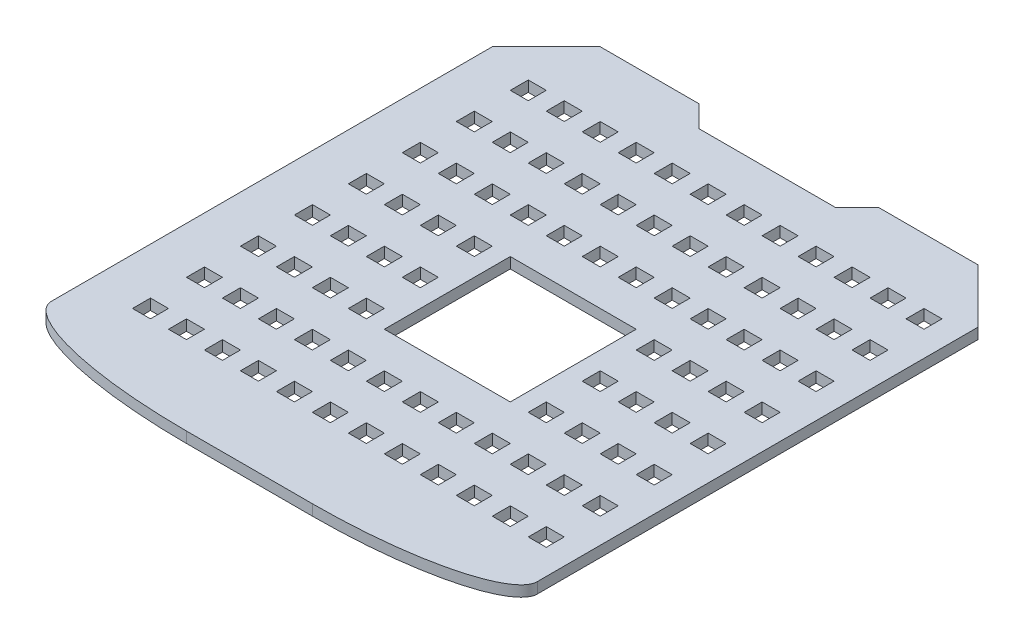
SolidWorks part; units mm, degrees
material "Balsa"
ref_plane "Front Plane" through (0, 0, 0) normal (0, 0, 1) x (1, 0, 0)
ref_plane "Top Plane" through (0, 0, 0) normal (0, 1, 0) x (1, 0, 0)
ref_plane "Right Plane" through (0, 0, 0) normal (1, 0, 0) x (0, 0, -1)
sketch "Sketch1" plane through (0, 0, 0) normal (0, 1, 0) x (1, 0, 0)
  line L1 (-67.5, 75) -> (67.5, 75)
  line L2 (-67.5, 75) -> (-67.5, -75)
  line L3 (-67.5, -75) -> (67.5, -75)
  line L4 (67.5, 75) -> (67.5, -75)
  line L5 (-67.5, 75) -> (67.5, -75) construction
  line L6 (-67.5, -75) -> (67.5, 75) construction
  point P0 (0, 0)
  dimension "D1" = 135
  dimension "D2" = 150
extrude "Boss-Extrude1" add sketch "Sketch1" along normal blind 3
sketch "Sketch2" plane through (0, 3, 0) normal (0, 1, 0) x (1, 0, 0)
  line L5 (-67.5, 75) -> (-67.5, -75) construction
  line L6 (-44.5, -53) -> (-44.5, -48)
  line L1140 (-54.5, -53) -> (-54.5, -48)
  line L1141 (-54.5, -53) -> (-49.5, -53)
  line L1142 (-49.5, -53) -> (-49.5, -48)
  line L1143 (-54.5, -48) -> (-49.5, -48)
  line L1144 (-44.5, -48) -> (-39.5, -48)
  line L1145 (-67.5, -75) -> (67.5, -75) construction
  line L1146 (-39.5, -53) -> (-39.5, -48)
  line L1249 (-44.5, -53) -> (-39.5, -53)
  line L1250 (-34.5, -53) -> (-34.5, -48)
  line L1251 (-34.5, -48) -> (-29.5, -48)
  line L1252 (-29.5, -53) -> (-29.5, -48)
  line L1253 (-34.5, -53) -> (-29.5, -53)
  line L1254 (-24.5, -53) -> (-24.5, -48)
  line L1255 (-24.5, -48) -> (-19.5, -48)
  line L1256 (-19.5, -53) -> (-19.5, -48)
  line L1257 (-24.5, -53) -> (-19.5, -53)
  line L1258 (-14.5, -53) -> (-14.5, -48)
  line L1259 (-14.5, -48) -> (-9.5, -48)
  line L1260 (-9.5, -53) -> (-9.5, -48)
  line L1261 (-14.5, -53) -> (-9.5, -53)
  line L1262 (-4.5, -53) -> (-4.5, -48)
  line L1263 (-4.5, -48) -> (0.5, -48)
  line L1264 (0.5, -53) -> (0.5, -48)
  line L1265 (-4.5, -53) -> (0.5, -53)
  line L1266 (5.5, -53) -> (5.5, -48)
  line L1267 (5.5, -48) -> (10.5, -48)
  line L1268 (10.5, -53) -> (10.5, -48)
  line L1269 (5.5, -53) -> (10.5, -53)
  line L1270 (15.5, -53) -> (15.5, -48)
  line L1271 (15.5, -48) -> (20.5, -48)
  line L1272 (20.5, -53) -> (20.5, -48)
  line L1273 (15.5, -53) -> (20.5, -53)
  line L1274 (25.5, -53) -> (25.5, -48)
  line L1275 (25.5, -48) -> (30.5, -48)
  line L1276 (30.5, -53) -> (30.5, -48)
  line L1277 (25.5, -53) -> (30.5, -53)
  line L1278 (35.5, -53) -> (35.5, -48)
  line L1279 (35.5, -48) -> (40.5, -48)
  line L1280 (40.5, -53) -> (40.5, -48)
  line L1281 (35.5, -53) -> (40.5, -53)
  line L1282 (45.5, -53) -> (45.5, -48)
  line L1283 (45.5, -48) -> (50.5, -48)
  line L1284 (50.5, -53) -> (50.5, -48)
  line L1285 (45.5, -53) -> (50.5, -53)
  line L1286 (55.5, -53) -> (55.5, -48)
  line L1287 (55.5, -48) -> (60.5, -48)
  line L1288 (60.5, -53) -> (60.5, -48)
  line L1289 (55.5, -53) -> (60.5, -53)
  line L1290 (-44.5, -38) -> (-44.5, -33)
  line L1291 (-44.5, -33) -> (-39.5, -33)
  line L1292 (-39.5, -38) -> (-39.5, -33)
  line L1293 (-44.5, -38) -> (-39.5, -38)
  line L1294 (-34.5, -38) -> (-34.5, -33)
  line L1295 (-34.5, -33) -> (-29.5, -33)
  line L1296 (-29.5, -38) -> (-29.5, -33)
  line L1297 (-34.5, -38) -> (-29.5, -38)
  line L1298 (-24.5, -38) -> (-24.5, -33)
  line L1299 (-24.5, -33) -> (-19.5, -33)
  line L1300 (-19.5, -38) -> (-19.5, -33)
  line L1301 (-24.5, -38) -> (-19.5, -38)
  line L1302 (-14.5, -38) -> (-14.5, -33)
  line L1303 (-14.5, -33) -> (-9.5, -33)
  line L1304 (-9.5, -38) -> (-9.5, -33)
  line L1305 (-14.5, -38) -> (-9.5, -38)
  line L1306 (-4.5, -38) -> (-4.5, -33)
  line L1307 (-4.5, -33) -> (0.5, -33)
  line L1308 (0.5, -38) -> (0.5, -33)
  line L1309 (-4.5, -38) -> (0.5, -38)
  line L1310 (5.5, -38) -> (5.5, -33)
  line L1311 (5.5, -33) -> (10.5, -33)
  line L1312 (10.5, -38) -> (10.5, -33)
  line L1313 (5.5, -38) -> (10.5, -38)
  line L1314 (15.5, -38) -> (15.5, -33)
  line L1315 (15.5, -33) -> (20.5, -33)
  line L1316 (20.5, -38) -> (20.5, -33)
  line L1317 (15.5, -38) -> (20.5, -38)
  line L1318 (25.5, -38) -> (25.5, -33)
  line L1319 (25.5, -33) -> (30.5, -33)
  line L1320 (30.5, -38) -> (30.5, -33)
  line L1321 (25.5, -38) -> (30.5, -38)
  line L1322 (35.5, -38) -> (35.5, -33)
  line L1323 (35.5, -33) -> (40.5, -33)
  line L1324 (40.5, -38) -> (40.5, -33)
  line L1325 (35.5, -38) -> (40.5, -38)
  line L1326 (45.5, -38) -> (45.5, -33)
  line L1327 (45.5, -33) -> (50.5, -33)
  line L1328 (50.5, -38) -> (50.5, -33)
  line L1329 (45.5, -38) -> (50.5, -38)
  line L1330 (55.5, -38) -> (55.5, -33)
  line L1331 (55.5, -33) -> (60.5, -33)
  line L1332 (60.5, -38) -> (60.5, -33)
  line L1333 (55.5, -38) -> (60.5, -38)
  line L1334 (-44.5, -23) -> (-44.5, -18)
  line L1335 (-44.5, -18) -> (-39.5, -18)
  line L1336 (-39.5, -23) -> (-39.5, -18)
  line L1337 (-44.5, -23) -> (-39.5, -23)
  line L1338 (-34.5, -23) -> (-34.5, -18)
  line L1339 (-34.5, -18) -> (-29.5, -18)
  line L1340 (-29.5, -23) -> (-29.5, -18)
  line L1341 (-34.5, -23) -> (-29.5, -23)
  line L1342 (-24.5, -23) -> (-24.5, -18)
  line L1343 (-24.5, -18) -> (-19.5, -18)
  line L1344 (-19.5, -23) -> (-19.5, -18)
  line L1345 (-24.5, -23) -> (-19.5, -23)
  line L1346 (-14.5, -23) -> (-14.5, -18)
  line L1347 (-14.5, -18) -> (-9.5, -18)
  line L1348 (-9.5, -23) -> (-9.5, -18)
  line L1349 (-14.5, -23) -> (-9.5, -23)
  line L1350 (-4.5, -23) -> (-4.5, -18)
  line L1351 (-4.5, -18) -> (0.5, -18)
  line L1352 (0.5, -23) -> (0.5, -18)
  line L1353 (-4.5, -23) -> (0.5, -23)
  line L1354 (5.5, -23) -> (5.5, -18)
  line L1355 (5.5, -18) -> (10.5, -18)
  line L1356 (10.5, -23) -> (10.5, -18)
  line L1357 (5.5, -23) -> (10.5, -23)
  line L1358 (15.5, -23) -> (15.5, -18)
  line L1359 (15.5, -18) -> (20.5, -18)
  line L1360 (20.5, -23) -> (20.5, -18)
  line L1361 (15.5, -23) -> (20.5, -23)
  line L1362 (25.5, -23) -> (25.5, -18)
  line L1363 (25.5, -18) -> (30.5, -18)
  line L1364 (30.5, -23) -> (30.5, -18)
  line L1365 (25.5, -23) -> (30.5, -23)
  line L1366 (35.5, -23) -> (35.5, -18)
  line L1367 (35.5, -18) -> (40.5, -18)
  line L1368 (40.5, -23) -> (40.5, -18)
  line L1369 (35.5, -23) -> (40.5, -23)
  line L1370 (45.5, -23) -> (45.5, -18)
  line L1371 (45.5, -18) -> (50.5, -18)
  line L1372 (50.5, -23) -> (50.5, -18)
  line L1373 (45.5, -23) -> (50.5, -23)
  line L1374 (55.5, -23) -> (55.5, -18)
  line L1375 (55.5, -18) -> (60.5, -18)
  line L1376 (60.5, -23) -> (60.5, -18)
  line L1377 (55.5, -23) -> (60.5, -23)
  line L1378 (-44.5, -8) -> (-44.5, -3)
  line L1379 (-44.5, -3) -> (-39.5, -3)
  line L1380 (-39.5, -8) -> (-39.5, -3)
  line L1381 (-44.5, -8) -> (-39.5, -8)
  line L1382 (-34.5, -8) -> (-34.5, -3)
  line L1383 (-34.5, -3) -> (-29.5, -3)
  line L1384 (-29.5, -8) -> (-29.5, -3)
  line L1385 (-34.5, -8) -> (-29.5, -8)
  line L1386 (-24.5, -8) -> (-24.5, -3)
  line L1387 (-24.5, -3) -> (-19.5, -3)
  line L1388 (-19.5, -8) -> (-19.5, -3)
  line L1389 (-24.5, -8) -> (-19.5, -8)
  line L1390 (-14.5, -8) -> (-14.5, -3)
  line L1391 (-14.5, -3) -> (-9.5, -3)
  line L1392 (-9.5, -8) -> (-9.5, -3)
  line L1393 (-14.5, -8) -> (-9.5, -8)
  line L1394 (-4.5, -8) -> (-4.5, -3)
  line L1395 (-4.5, -3) -> (0.5, -3)
  line L1396 (0.5, -8) -> (0.5, -3)
  line L1397 (-4.5, -8) -> (0.5, -8)
  line L1398 (5.5, -8) -> (5.5, -3)
  line L1399 (5.5, -3) -> (10.5, -3)
  line L1400 (10.5, -8) -> (10.5, -3)
  line L1401 (5.5, -8) -> (10.5, -8)
  line L1402 (15.5, -8) -> (15.5, -3)
  line L1403 (15.5, -3) -> (20.5, -3)
  line L1404 (20.5, -8) -> (20.5, -3)
  line L1405 (15.5, -8) -> (20.5, -8)
  line L1406 (25.5, -8) -> (25.5, -3)
  line L1407 (25.5, -3) -> (30.5, -3)
  line L1408 (30.5, -8) -> (30.5, -3)
  line L1409 (25.5, -8) -> (30.5, -8)
  line L1410 (35.5, -8) -> (35.5, -3)
  line L1411 (35.5, -3) -> (40.5, -3)
  line L1412 (40.5, -8) -> (40.5, -3)
  line L1413 (35.5, -8) -> (40.5, -8)
  line L1414 (45.5, -8) -> (45.5, -3)
  line L1415 (45.5, -3) -> (50.5, -3)
  line L1416 (50.5, -8) -> (50.5, -3)
  line L1417 (45.5, -8) -> (50.5, -8)
  line L1418 (55.5, -8) -> (55.5, -3)
  line L1419 (55.5, -3) -> (60.5, -3)
  line L1420 (60.5, -8) -> (60.5, -3)
  line L1421 (55.5, -8) -> (60.5, -8)
  line L1422 (-44.5, 7) -> (-44.5, 12)
  line L1423 (-44.5, 12) -> (-39.5, 12)
  line L1424 (-39.5, 7) -> (-39.5, 12)
  line L1425 (-44.5, 7) -> (-39.5, 7)
  line L1426 (-34.5, 7) -> (-34.5, 12)
  line L1427 (-34.5, 12) -> (-29.5, 12)
  line L1428 (-29.5, 7) -> (-29.5, 12)
  line L1429 (-34.5, 7) -> (-29.5, 7)
  line L1430 (-24.5, 7) -> (-24.5, 12)
  line L1431 (-24.5, 12) -> (-19.5, 12)
  line L1432 (-19.5, 7) -> (-19.5, 12)
  line L1433 (-24.5, 7) -> (-19.5, 7)
  line L1434 (-14.5, 7) -> (-14.5, 12)
  line L1435 (-14.5, 12) -> (-9.5, 12)
  line L1436 (-9.5, 7) -> (-9.5, 12)
  line L1437 (-14.5, 7) -> (-9.5, 7)
  line L1438 (-4.5, 7) -> (-4.5, 12)
  line L1439 (-4.5, 12) -> (0.5, 12)
  line L1440 (0.5, 7) -> (0.5, 12)
  line L1441 (-4.5, 7) -> (0.5, 7)
  line L1442 (5.5, 7) -> (5.5, 12)
  line L1443 (5.5, 12) -> (10.5, 12)
  line L1444 (10.5, 7) -> (10.5, 12)
  line L1445 (5.5, 7) -> (10.5, 7)
  line L1446 (15.5, 7) -> (15.5, 12)
  line L1447 (15.5, 12) -> (20.5, 12)
  line L1448 (20.5, 7) -> (20.5, 12)
  line L1449 (15.5, 7) -> (20.5, 7)
  line L1450 (25.5, 7) -> (25.5, 12)
  line L1451 (25.5, 12) -> (30.5, 12)
  line L1452 (30.5, 7) -> (30.5, 12)
  line L1453 (25.5, 7) -> (30.5, 7)
  line L1454 (35.5, 7) -> (35.5, 12)
  line L1455 (35.5, 12) -> (40.5, 12)
  line L1456 (40.5, 7) -> (40.5, 12)
  line L1457 (35.5, 7) -> (40.5, 7)
  line L1458 (45.5, 7) -> (45.5, 12)
  line L1459 (45.5, 12) -> (50.5, 12)
  line L1460 (50.5, 7) -> (50.5, 12)
  line L1461 (45.5, 7) -> (50.5, 7)
  line L1462 (55.5, 7) -> (55.5, 12)
  line L1463 (55.5, 12) -> (60.5, 12)
  line L1464 (60.5, 7) -> (60.5, 12)
  line L1465 (55.5, 7) -> (60.5, 7)
  line L1466 (-44.5, 22) -> (-44.5, 27)
  line L1467 (-44.5, 27) -> (-39.5, 27)
  line L1468 (-39.5, 22) -> (-39.5, 27)
  line L1469 (-44.5, 22) -> (-39.5, 22)
  line L1470 (-34.5, 22) -> (-34.5, 27)
  line L1471 (-34.5, 27) -> (-29.5, 27)
  line L1472 (-29.5, 22) -> (-29.5, 27)
  line L1473 (-34.5, 22) -> (-29.5, 22)
  line L1474 (-24.5, 22) -> (-24.5, 27)
  line L1475 (-24.5, 27) -> (-19.5, 27)
  line L1476 (-19.5, 22) -> (-19.5, 27)
  line L1477 (-24.5, 22) -> (-19.5, 22)
  line L1478 (-14.5, 22) -> (-14.5, 27)
  line L1479 (-14.5, 27) -> (-9.5, 27)
  line L1480 (-9.5, 22) -> (-9.5, 27)
  line L1481 (-14.5, 22) -> (-9.5, 22)
  line L1482 (-4.5, 22) -> (-4.5, 27)
  line L1483 (-4.5, 27) -> (0.5, 27)
  line L1484 (0.5, 22) -> (0.5, 27)
  line L1485 (-4.5, 22) -> (0.5, 22)
  line L1486 (5.5, 22) -> (5.5, 27)
  line L1487 (5.5, 27) -> (10.5, 27)
  line L1488 (10.5, 22) -> (10.5, 27)
  line L1489 (5.5, 22) -> (10.5, 22)
  line L1490 (15.5, 22) -> (15.5, 27)
  line L1491 (15.5, 27) -> (20.5, 27)
  line L1492 (20.5, 22) -> (20.5, 27)
  line L1493 (15.5, 22) -> (20.5, 22)
  line L1494 (25.5, 22) -> (25.5, 27)
  line L1495 (25.5, 27) -> (30.5, 27)
  line L1496 (30.5, 22) -> (30.5, 27)
  line L1497 (25.5, 22) -> (30.5, 22)
  line L1498 (35.5, 22) -> (35.5, 27)
  line L1499 (35.5, 27) -> (40.5, 27)
  line L1500 (40.5, 22) -> (40.5, 27)
  line L1501 (35.5, 22) -> (40.5, 22)
  line L1502 (45.5, 22) -> (45.5, 27)
  line L1503 (45.5, 27) -> (50.5, 27)
  line L1504 (50.5, 22) -> (50.5, 27)
  line L1505 (45.5, 22) -> (50.5, 22)
  line L1506 (55.5, 22) -> (55.5, 27)
  line L1507 (55.5, 27) -> (60.5, 27)
  line L1508 (60.5, 22) -> (60.5, 27)
  line L1509 (55.5, 22) -> (60.5, 22)
  line L1510 (-44.5, 37) -> (-44.5, 42)
  line L1511 (-44.5, 42) -> (-39.5, 42)
  line L1512 (-39.5, 37) -> (-39.5, 42)
  line L1513 (-44.5, 37) -> (-39.5, 37)
  line L1514 (-34.5, 37) -> (-34.5, 42)
  line L1515 (-34.5, 42) -> (-29.5, 42)
  line L1516 (-29.5, 37) -> (-29.5, 42)
  line L1517 (-34.5, 37) -> (-29.5, 37)
  line L1518 (-24.5, 37) -> (-24.5, 42)
  line L1519 (-24.5, 42) -> (-19.5, 42)
  line L1520 (-19.5, 37) -> (-19.5, 42)
  line L1521 (-24.5, 37) -> (-19.5, 37)
  line L1522 (-14.5, 37) -> (-14.5, 42)
  line L1523 (-14.5, 42) -> (-9.5, 42)
  line L1524 (-9.5, 37) -> (-9.5, 42)
  line L1525 (-14.5, 37) -> (-9.5, 37)
  line L1526 (-4.5, 37) -> (-4.5, 42)
  line L1527 (-4.5, 42) -> (0.5, 42)
  line L1528 (0.5, 37) -> (0.5, 42)
  line L1529 (-4.5, 37) -> (0.5, 37)
  line L1530 (5.5, 37) -> (5.5, 42)
  line L1531 (5.5, 42) -> (10.5, 42)
  line L1532 (10.5, 37) -> (10.5, 42)
  line L1533 (5.5, 37) -> (10.5, 37)
  line L1534 (15.5, 37) -> (15.5, 42)
  line L1535 (15.5, 42) -> (20.5, 42)
  line L1536 (20.5, 37) -> (20.5, 42)
  line L1537 (15.5, 37) -> (20.5, 37)
  line L1538 (25.5, 37) -> (25.5, 42)
  line L1539 (25.5, 42) -> (30.5, 42)
  line L1540 (30.5, 37) -> (30.5, 42)
  line L1541 (25.5, 37) -> (30.5, 37)
  line L1542 (35.5, 37) -> (35.5, 42)
  line L1543 (35.5, 42) -> (40.5, 42)
  line L1544 (40.5, 37) -> (40.5, 42)
  line L1545 (35.5, 37) -> (40.5, 37)
  line L1546 (45.5, 37) -> (45.5, 42)
  line L1547 (45.5, 42) -> (50.5, 42)
  line L1548 (50.5, 37) -> (50.5, 42)
  line L1549 (45.5, 37) -> (50.5, 37)
  line L1550 (55.5, 37) -> (55.5, 42)
  line L1551 (55.5, 42) -> (60.5, 42)
  line L1552 (60.5, 37) -> (60.5, 42)
  line L1553 (55.5, 37) -> (60.5, 37)
  line L1554 (-44.5, 52) -> (-44.5, 57)
  line L1555 (-44.5, 57) -> (-39.5, 57)
  line L1556 (-39.5, 52) -> (-39.5, 57)
  line L1557 (-44.5, 52) -> (-39.5, 52)
  line L1558 (-34.5, 52) -> (-34.5, 57)
  line L1559 (-34.5, 57) -> (-29.5, 57)
  line L1560 (-29.5, 52) -> (-29.5, 57)
  line L1561 (-34.5, 52) -> (-29.5, 52)
  line L1562 (-24.5, 52) -> (-24.5, 57)
  line L1563 (-24.5, 57) -> (-19.5, 57)
  line L1564 (-19.5, 52) -> (-19.5, 57)
  line L1565 (-24.5, 52) -> (-19.5, 52)
  line L1566 (-14.5, 52) -> (-14.5, 57)
  line L1567 (-14.5, 57) -> (-9.5, 57)
  line L1568 (-9.5, 52) -> (-9.5, 57)
  line L1569 (-14.5, 52) -> (-9.5, 52)
  line L1570 (-4.5, 52) -> (-4.5, 57)
  line L1571 (-4.5, 57) -> (0.5, 57)
  line L1572 (0.5, 52) -> (0.5, 57)
  line L1573 (-4.5, 52) -> (0.5, 52)
  line L1574 (5.5, 52) -> (5.5, 57)
  line L1575 (5.5, 57) -> (10.5, 57)
  line L1576 (10.5, 52) -> (10.5, 57)
  line L1577 (5.5, 52) -> (10.5, 52)
  line L1578 (15.5, 52) -> (15.5, 57)
  line L1579 (15.5, 57) -> (20.5, 57)
  line L1580 (20.5, 52) -> (20.5, 57)
  line L1581 (15.5, 52) -> (20.5, 52)
  line L1582 (25.5, 52) -> (25.5, 57)
  line L1583 (25.5, 57) -> (30.5, 57)
  line L1584 (30.5, 52) -> (30.5, 57)
  line L1585 (25.5, 52) -> (30.5, 52)
  line L1586 (35.5, 52) -> (35.5, 57)
  line L1587 (35.5, 57) -> (40.5, 57)
  line L1588 (40.5, 52) -> (40.5, 57)
  line L1589 (35.5, 52) -> (40.5, 52)
  line L1590 (45.5, 52) -> (45.5, 57)
  line L1591 (45.5, 57) -> (50.5, 57)
  line L1592 (50.5, 52) -> (50.5, 57)
  line L1593 (45.5, 52) -> (50.5, 52)
  line L1594 (55.5, 52) -> (55.5, 57)
  line L1595 (55.5, 57) -> (60.5, 57)
  line L1596 (60.5, 52) -> (60.5, 57)
  line L1597 (55.5, 52) -> (60.5, 52)
  line L1598 (-54.5, -38) -> (-54.5, -33)
  line L1599 (-54.5, -33) -> (-49.5, -33)
  line L1600 (-49.5, -38) -> (-49.5, -33)
  line L1601 (-54.5, -38) -> (-49.5, -38)
  line L1602 (-54.5, -23) -> (-54.5, -18)
  line L1603 (-54.5, -18) -> (-49.5, -18)
  line L1604 (-49.5, -23) -> (-49.5, -18)
  line L1605 (-54.5, -23) -> (-49.5, -23)
  line L1606 (-54.5, -8) -> (-54.5, -3)
  line L1607 (-54.5, -3) -> (-49.5, -3)
  line L1608 (-49.5, -8) -> (-49.5, -3)
  line L1609 (-54.5, -8) -> (-49.5, -8)
  line L1610 (-54.5, 7) -> (-54.5, 12)
  line L1611 (-54.5, 12) -> (-49.5, 12)
  line L1612 (-49.5, 7) -> (-49.5, 12)
  line L1613 (-54.5, 7) -> (-49.5, 7)
  line L1614 (-54.5, 22) -> (-54.5, 27)
  line L1615 (-54.5, 27) -> (-49.5, 27)
  line L1616 (-49.5, 22) -> (-49.5, 27)
  line L1617 (-54.5, 22) -> (-49.5, 22)
  line L1618 (-54.5, 37) -> (-54.5, 42)
  line L1619 (-54.5, 42) -> (-49.5, 42)
  line L1620 (-49.5, 37) -> (-49.5, 42)
  line L1621 (-54.5, 37) -> (-49.5, 37)
  line L1622 (-54.5, 52) -> (-54.5, 57)
  line L1623 (-54.5, 57) -> (-49.5, 57)
  line L1624 (-49.5, 52) -> (-49.5, 57)
  line L1625 (-54.5, 52) -> (-49.5, 52)
  dimension "D1" = 13
  dimension "D2" = 5
  dimension "D3" = 12
  dimension "D7" = 22
extrude "Cut-Extrude1" cut sketch "Sketch2" against normal through all
fillet "Fillet1" radius 12.5 1 edges at (-67.5, 1.5, 75) second distance 50 first distance on face at (-67.5, 1.5, 0)
fillet "Fillet2" radius 12.5 1 edges at (67.5, 1.5, 75) second distance 50 first distance on face at (67.5, 1.5, 0)
sketch "Sketch4" plane through (0, 3, 0) normal (0, 1, 0) x (1, 0, 0)
  line L0 (-67.5, 60) -> (-67.5, 75)
  line L1 (-67.5, 75) -> (-67.5, -62.5) construction
  line L2 (-67.5, 75) -> (-52.5, 75)
  line L3 (67.5, 75) -> (-67.5, 75) construction
  line L4 (-52.5, 75) -> (-67.5, 60)
  line L5 (0, 75) -> (0, -75) construction
  line L6 (-17.5, -75) -> (17.5, -75) construction
  line L7 (67.5, 75) -> (52.5, 75)
  line L8 (67.5, 60) -> (67.5, 75)
  line L9 (52.5, 75) -> (67.5, 60)
  dimension "D1" = 45
  dimension "D2" = 15
extrude "Cut-Extrude2" cut sketch "Sketch4" against normal through all
sketch "Sketch5" plane through (0, 3, 0) normal (0, 1, 0) x (1, 0, 0)
  line L6 (0, -75) -> (0, 75) construction
  line L7 (-17.5, -75) -> (17.5, -75) construction
  line L8 (52.5, 75) -> (-52.5, 75) construction
  line L9 (-25, 75) -> (25, 75)
  line L11 (-19, 69) -> (19, 69)
  line L13 (-25, 75) -> (9.8447, 59.8447) construction
  line L14 (-9.8447, 59.8447) -> (25, 75) construction
  line L15 (-25, 75) -> (-19, 69)
  line L16 (25, 75) -> (19, 69)
  point P0 (0, 64.1266)
  point P1 (0, 75)
  dimension "D1" = 50
  dimension "D2" = 45
  dimension "D3" = 6
extrude "Cut-Extrude3" cut sketch "Sketch5" against normal through all
sketch "Sketch6" plane through (0, 3, 0) normal (0, 1, 0) x (1, 0, 0)
  line L1 (-14.5, 12) -> (20.5, 12)
  line L2 (-14.5, 12) -> (-14.5, -23)
  line L3 (-14.5, -23) -> (20.5, -23)
  line L4 (20.5, 12) -> (20.5, -23)
extrude "Cut-Extrude4" cut sketch "Sketch6" against normal through all
